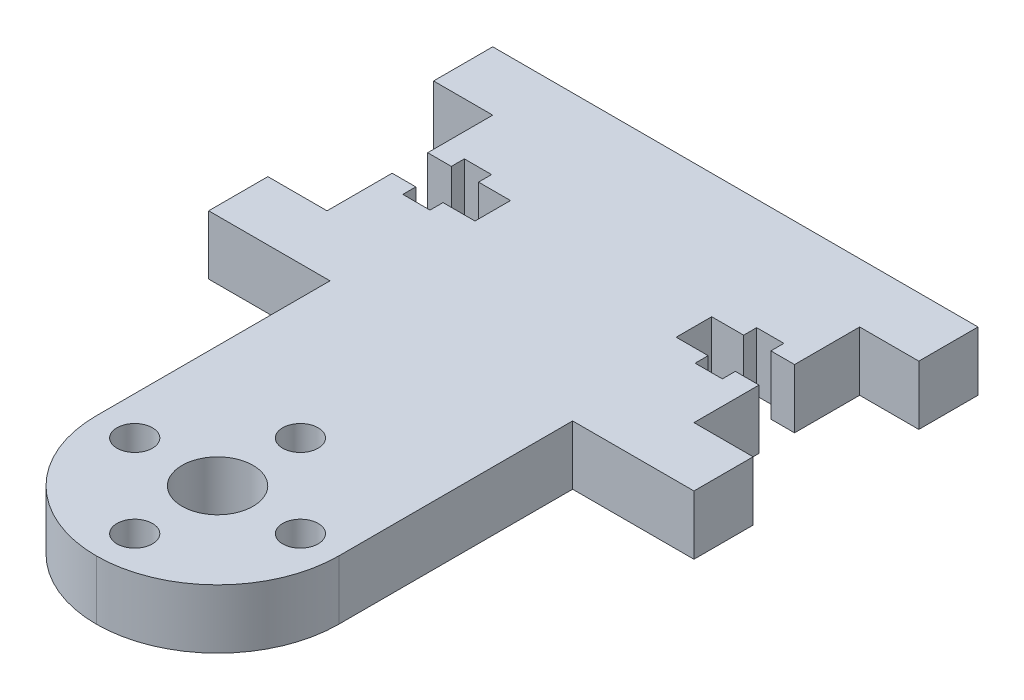
SolidWorks part; units mm, degrees
ref_plane "Front Plane" through (0, 0, 0) normal (0, 0, 1) x (1, 0, 0)
ref_plane "Top Plane" through (0, 0, 0) normal (0, 1, 0) x (1, 0, 0)
ref_plane "Right Plane" through (0, 0, 0) normal (1, 0, 0) x (0, 0, -1)
sketch "Sketch1" plane through (0, 0, 0) normal (0, 1, 0) x (1, 0, 0)
  line L0 (51.3755, 21.289) -> (44.3755, 18.289) construction
  line L1 (44.3755, 7.789) -> (75.3755, 7.789)
  line L2 (44.3755, 31.789) -> (75.3755, 31.789)
  line L3 (75.3755, 12.789) -> (75.3755, 18.289)
  line L4 (59.8755, 31.789) -> (59.8755, 7.789) construction
  line L5 (51.3755, 18.289) -> (44.3755, 21.289) construction
  line L6 (44.3755, 7.789) -> (39.3755, 7.789)
  line L7 (39.3755, 7.789) -> (39.3755, 12.789)
  line L8 (44.3755, 12.789) -> (44.3755, 18.289)
  line L9 (71.0755, 17.189) -> (73.3755, 17.189)
  line L10 (68.3755, 18.289) -> (71.0755, 18.289)
  line L11 (68.3755, 18.289) -> (68.3755, 21.289)
  line L12 (68.3755, 21.289) -> (71.0755, 21.289)
  line L13 (68.3755, 18.289) -> (75.3755, 21.289) construction
  line L14 (68.3755, 21.289) -> (75.3755, 18.289) construction
  line L15 (71.0755, 21.289) -> (71.0755, 22.389)
  line L16 (71.0755, 22.389) -> (73.3755, 22.389)
  line L17 (73.3755, 21.289) -> (73.3755, 22.389)
  line L18 (73.3755, 18.289) -> (73.3755, 17.189)
  line L19 (71.0755, 18.289) -> (71.0755, 17.189)
  line L20 (73.3755, 21.289) -> (75.3755, 21.289)
  line L21 (73.3755, 18.289) -> (75.3755, 18.289)
  line L22 (75.3755, 21.289) -> (75.3755, 26.789)
  line L23 (75.3755, 12.789) -> (80.3755, 12.789)
  line L24 (75.3755, 31.789) -> (80.3755, 31.789)
  line L25 (75.3755, 26.789) -> (80.3755, 26.789)
  line L26 (80.3755, 31.789) -> (80.3755, 26.789)
  line L27 (80.3755, 7.789) -> (80.3755, 12.789)
  line L28 (75.3755, 7.789) -> (80.3755, 7.789)
  line L29 (39.3755, 31.789) -> (39.3755, 26.789)
  line L30 (44.3755, 26.789) -> (39.3755, 26.789)
  line L31 (44.3755, 31.789) -> (39.3755, 31.789)
  line L32 (44.3755, 12.789) -> (39.3755, 12.789)
  line L33 (44.3755, 21.289) -> (44.3755, 26.789)
  line L34 (46.3755, 18.289) -> (44.3755, 18.289)
  line L35 (46.3755, 21.289) -> (44.3755, 21.289)
  line L36 (48.6755, 18.289) -> (48.6755, 17.189)
  line L37 (46.3755, 18.289) -> (46.3755, 17.189)
  line L38 (46.3755, 21.289) -> (46.3755, 22.389)
  line L39 (48.6755, 22.389) -> (46.3755, 22.389)
  line L40 (48.6755, 21.289) -> (48.6755, 22.389)
  line L41 (51.3755, 21.289) -> (48.6755, 21.289)
  line L42 (51.3755, 18.289) -> (51.3755, 21.289)
  line L43 (51.3755, 18.289) -> (48.6755, 18.289)
  line L44 (48.6755, 17.189) -> (46.3755, 17.189)
  line L45 (68.3755, 19.789) -> (59.8755, 19.789) construction
  point P23 (47.8755, 19.789)
  point P25 (71.8755, 19.789)
  point P44 (59.8755, 19.789)
  dimension "D2" = 31
  dimension "D3" = 3
  dimension "D4" = 5
  dimension "D5" = 5
  dimension "D6" = 2
  dimension "D7" = 2.3
  dimension "D8" = 2.7
  dimension "D9" = 1.1
  dimension "D10" = 5
  dimension "D11" = 24
extrude "Boss-Extrude1" add sketch "Sketch1" along normal blind 5
sketch "Sketch2" plane through (0, 5, 0) normal (0, 1, 0) x (1, 0, 0)
  line L0 (59.8755, 26.125) -> (59.8755, 6.125) construction
  line L1 (59.8755, 6.125) -> (59.8755, -7.211) construction
  line L2 (59.8755, -22.211) -> (59.8755, -11.961) construction
  line L3 (49.6255, -22.211) -> (70.1255, -22.211)
  line L4 (49.6255, -22.211) -> (49.6255, 7.789)
  line L5 (49.6255, 7.789) -> (70.1255, 7.789)
  line L6 (70.1255, -22.211) -> (70.1255, 7.789)
  line L7 (49.6255, -22.211) -> (70.1255, 7.789) construction
  line L8 (49.6255, 7.789) -> (70.1255, -22.211) construction
  line L9 (59.8755, -11.961) -> (58.7867, -13.0498) construction
  line L10 (59.8755, -11.961) -> (67.1337, -19.2192) construction
  line L11 (59.8755, 31.789) -> (59.8755, 7.789) construction
  line L12 (80.3755, 31.789) -> (39.3755, 31.789) construction
  line L13 (39.3755, 7.789) -> (80.3755, 7.789) construction
  circle A0 centre (59.8755, -11.961) radius 3
  circle A1 centre (59.8755, -18.961) radius 1.5
  circle A6 centre (52.8755, -11.961) radius 1.5
  circle A7 centre (66.8755, -11.961) radius 1.5
  circle A8 centre (59.8755, -4.961) radius 1.5
  dimension "D3" = 6
  dimension "D5" = 3
  dimension "D1" = 30
  dimension "D2" = 20.5
  dimension "D4" = 10.25
  dimension "D6" = 7
  dimension "D7" = 45
  dimension "D8" = 45
extrude "Boss-Extrude2" add sketch "Sketch2" against normal blind 5
fillet "Fillet1" radius 10.25 2 edges at (49.6255, 2.5, 22.211) (70.1255, 2.5, 22.211)
